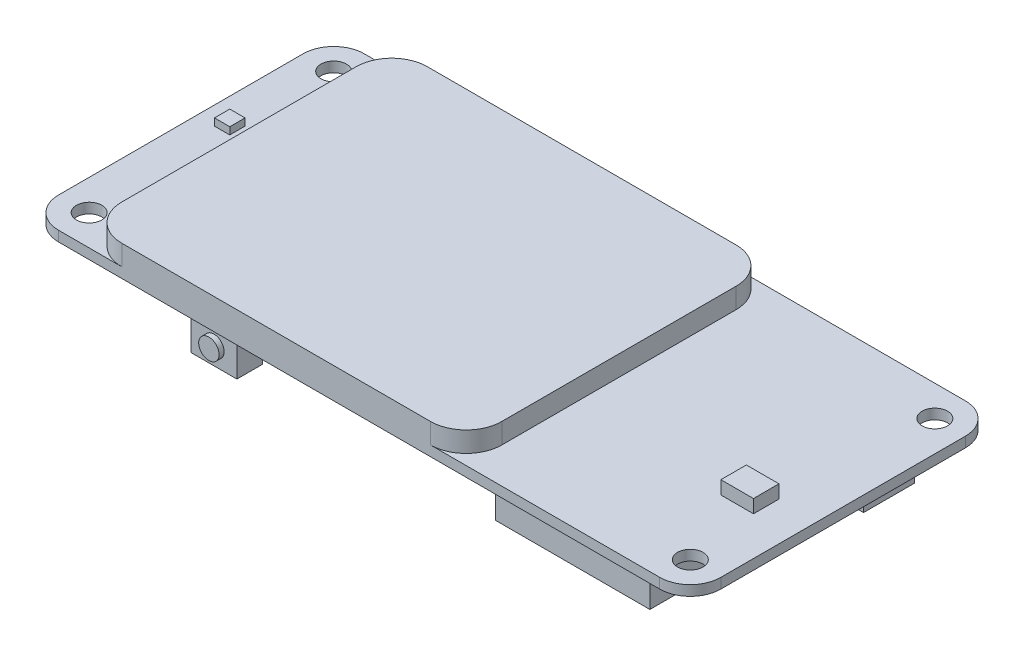
SolidWorks part; units mm, degrees
ref_plane "前视基准面" through (0, 0, 0) normal (0, 0, 1) x (1, 0, 0)
ref_plane "上视基准面" through (0, 0, 0) normal (0, 1, 0) x (1, 0, 0)
ref_plane "右视基准面" through (0, 0, 0) normal (1, 0, 0) x (0, 0, -1)
other "Configuration Table"
sketch "草图1" plane through (0, 0, 0) normal (0, 1, 0) x (1, 0, 0)
  line L1 (-29.5, 15) -> (29.5, 15)
  line L2 (-32.5, 12) -> (-32.5, -12)
  line L3 (-29.5, -15) -> (29.5, -15)
  line L4 (32.5, 12) -> (32.5, -12)
  line L5 (-32.5, 15) -> (32.5, -15) construction
  line L6 (-32.5, -15) -> (32.5, 15) construction
  arc A0 (29.5, -15) -> (32.5, -12) centre (29.5, -12) ccw
  arc A1 (29.5, 15) -> (32.5, 12) centre (29.5, 12) cw
  arc A2 (-32.5, -12) -> (-29.5, -15) centre (-29.5, -12) ccw
  arc A3 (-29.5, 15) -> (-32.5, 12) centre (-29.5, 12) ccw
  circle A4 centre (-29.5, 12) radius 1.25
  circle A5 centre (29.5, 12) radius 1.25
  circle A6 centre (-29.5, -12) radius 1.25
  circle A7 centre (29.5, -12) radius 1.25
  point P0 (0, 0)
  dimension "D3" = 3
  dimension "D4" = 2.5
  dimension "D1" = 65
  dimension "D2" = 30
extrude "board" add sketch "草图1" along normal blind 1
sketch "草图2" plane through (0, 1, 0) normal (0, 1, 0) x (1, 0, 0)
  line L0 (29.5, 15) -> (-29.5, 15) construction
  line L1 (-26.8, 15) -> (10.5, 15)
  line L2 (-26.8, 15) -> (-26.8, -15)
  line L3 (-26.8, -15) -> (10.5, -15)
  line L4 (10.5, 15) -> (10.5, -15)
  line L5 (-29.5, -15) -> (29.5, -15) construction
  line L6 (-32.5, 12) -> (-32.5, -12) construction
  line L7 (32.5, -12) -> (32.5, 12) construction
  dimension "D1" = 22
  dimension "D2" = 5.7
extrude "screen" add sketch "草图2" along normal blind 2
fillet "screen-radius" radius 3.5 4 edges at (-26.8, 2, -15) (10.5, 2, -15) (10.5, 2, 15) (-26.8, 2, 15)
sketch "草图3" plane through (0, 0, 0) normal (0, -1, 0) x (1, 0, 0)
  line L0 (32.5, 12) -> (32.5, -12) construction
  line L1 (-25.5, -9) -> (25.5, -9)
  line L2 (-25.5, -9) -> (-25.5, -14)
  line L3 (-25.5, -14) -> (25.5, -14)
  line L4 (25.5, -9) -> (25.5, -14)
  line L6 (29.5, -15) -> (-29.5, -15) construction
  dimension "D1" = 5
  dimension "D2" = 51
  dimension "D3" = 7
  dimension "D4" = 1
extrude "plug" add sketch "草图3" along normal blind 7.5
sketch "草图4" plane through (0, 0, 0) normal (0, -1, 0) x (1, 0, 0)
  line L0 (32.5, 12) -> (32.5, -12) construction
  line L1 (10.61, 12.2162) -> (25.75, 12.2162)
  line L2 (10.61, 12.2162) -> (10.61, -7.7838)
  line L3 (10.61, -7.7838) -> (25.75, -7.7838)
  line L4 (25.75, 12.2162) -> (25.75, -7.7838)
  dimension "D1" = 15.14
  dimension "D2" = 20
  dimension "D3" = 6.75
extrude "speaker" add sketch "草图4" along normal blind 5
sketch "草图5" plane through (0, 0, 0) normal (0, -1, 0) x (1, 0, 0)
  line L0 (-29.5, 15) -> (29.5, 15) construction
  line L1 (-17, 14.5) -> (-12.5, 14.5)
  line L2 (-17, 14.5) -> (-17, 12)
  line L3 (-17, 12) -> (-12.5, 12)
  line L4 (-12.5, 14.5) -> (-12.5, 12)
  line L5 (-32.5, -12) -> (-32.5, 12) construction
  dimension "D1" = 4.5
  dimension "D2" = 2.5
  dimension "D3" = 0.5
  dimension "D4" = 15.5
extrude "button" add sketch "草图5" along normal blind 3.4
sketch "草图6" plane through (0, 0, 14.5) normal (0, 0, 1) x (1, 0, 0)
  line L0 (-12.5, 0) -> (-17, 0) construction
  line L1 (-12.5, -3.4) -> (-17, -3.4) construction
  circle A0 centre (-14.75, -1.7) radius 1
  point P7 (-14.75, -3.4)
  dimension "D1" = 2
  dimension "D2" = 1.7
extrude "button-tap" add sketch "草图6" along normal blind 0.5
sketch "草图7" plane through (0, 1, 0) normal (0, 1, 0) x (1, 0, 0)
  line L0 (-23.3, 15) -> (-29.5, 15) construction
  line L1 (-30.7, 3) -> (-29.2, 3)
  line L2 (-30.7, 3) -> (-30.7, 1.5)
  line L3 (-30.7, 1.5) -> (-29.2, 1.5)
  line L4 (-29.2, 3) -> (-29.2, 1.5)
  line L5 (-32.5, 12) -> (-32.5, -12) construction
  dimension "D1" = 1.5
  dimension "D2" = 1.5
  dimension "D3" = 12
  dimension "D4" = 1.8
extrude "rgb-led" add sketch "草图7" along normal blind 0.7
sketch "草图8" plane through (0, 1, 0) normal (0, 1, 0) x (1, 0, 0)
  line L0 (29.5, 15) -> (7, 15) construction
  line L1 (28.7, -2.5) -> (25.5, -2.5)
  line L2 (28.7, -2.5) -> (28.7, -5)
  line L3 (28.7, -5) -> (25.5, -5)
  line L4 (25.5, -2.5) -> (25.5, -5)
  line L5 (32.5, -12) -> (32.5, 12) construction
  dimension "D1" = 3.2
  dimension "D2" = 2.5
  dimension "D3" = 17.5
  dimension "D4" = 3.8
extrude "mic" add sketch "草图8" along normal blind 1.3
